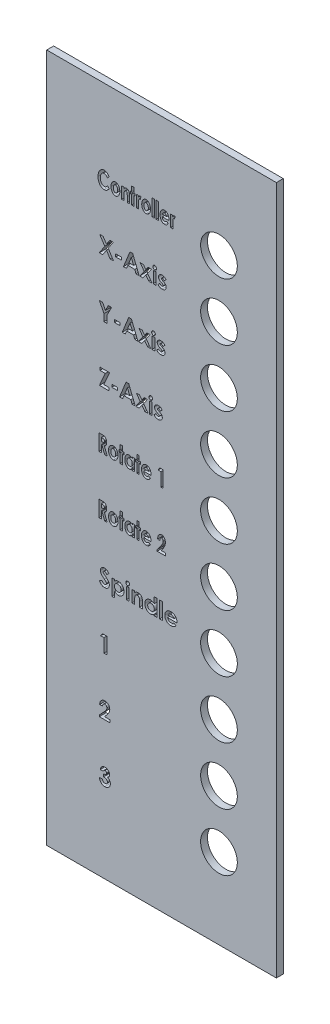
SolidWorks part; units mm, degrees
ref_plane "Front Plane" through (0, 0, 0) normal (0, 0, 1) x (1, 0, 0)
ref_plane "Top Plane" through (0, 0, 0) normal (0, 1, 0) x (1, 0, 0)
ref_plane "Right Plane" through (0, 0, 0) normal (1, 0, 0) x (0, 0, -1)
sketch "Sketch1" plane through (0, 0, 0) normal (0, 0, 1) x (1, 0, 0)
  line L1 (-50, -150) -> (50, -150)
  line L2 (-50, -150) -> (-50, 150)
  line L3 (-50, 150) -> (50, 150)
  line L4 (50, -150) -> (50, 150)
  point P4 (0, 150)
  point P6 (50, 0)
  dimension "D1" = 100
  dimension "D2" = 300
extrude "Boss-Extrude1" add sketch "Sketch1" along normal blind 3
sketch "Sketch2" plane through (0, 0, 3) normal (0, 0, 1) x (1, 0, 0)
  line L0 (25, -1000) -> (25, 49000) construction
  line L1 (50, 150) -> (-50, 150) construction
  line L2 (50, -150) -> (50, 150) construction
  line L3 (-30, 110) -> (25, 110) construction
  line L4 (-30, -40) -> (25, -40) construction
  line L5 (-30, 85) -> (25, 85) construction
  line L6 (-30, 60) -> (25, 60) construction
  line L7 (-30, 35) -> (25, 35) construction
  line L8 (-30, 10) -> (25, 10) construction
  line L9 (-30, -15) -> (25, -15) construction
  line L10 (-50, 150) -> (-50, -150) construction
  line L11 (-30, -65) -> (25, -65) construction
  line L12 (-30, -90) -> (25, -90) construction
  line L13 (-30, -115) -> (25, -115) construction
  circle A0 centre (25, 110) radius 8
  circle A2 centre (25, 85) radius 8
  circle A3 centre (25, 60) radius 8
  circle A4 centre (25, 35) radius 8
  circle A5 centre (25, 10) radius 8
  circle A6 centre (25, -15) radius 8
  circle A7 centre (25, -40) radius 8
  circle A8 centre (25, -65) radius 8
  circle A9 centre (25, -90) radius 8
  circle A10 centre (25, -115) radius 8
  text T0 "<b> Controller</b>" font "Century Gothic" height 7
  text T1 "<b> X-Axis</b>" font "Century Gothic" height 7
  text T2 "<b> Y-Axis</b>" font "Century Gothic" height 7
  text T3 "<b> Z-Axis</b>" font "Century Gothic" height 7
  text T4 "<b> Rotate 1</b>" font "Century Gothic" height 7
  text T5 "<b> Rotate 2</b>" font "Century Gothic" height 7
  text T6 "<b> Spindle</b>" font "Century Gothic" height 7
  text T7 "<b> 1</b>" font "Century Gothic" height 7
  text T8 " <b>2</b>" font "Century Gothic" height 7
  text T9 " <b>3</b>" font "Century Gothic" height 7
  point P33 (-33.2489, 77.5)
  dimension "D1" = 16
  dimension "D2" = 40
  dimension "D4" = 25
  dimension "D6" = 20
  dimension "D7" = 25
  dimension "D8" = 25
  dimension "D3" = 10
  dimension "D5" = 10
extrude "Cut-Extrude1" cut sketch "Sketch2" against normal through all
